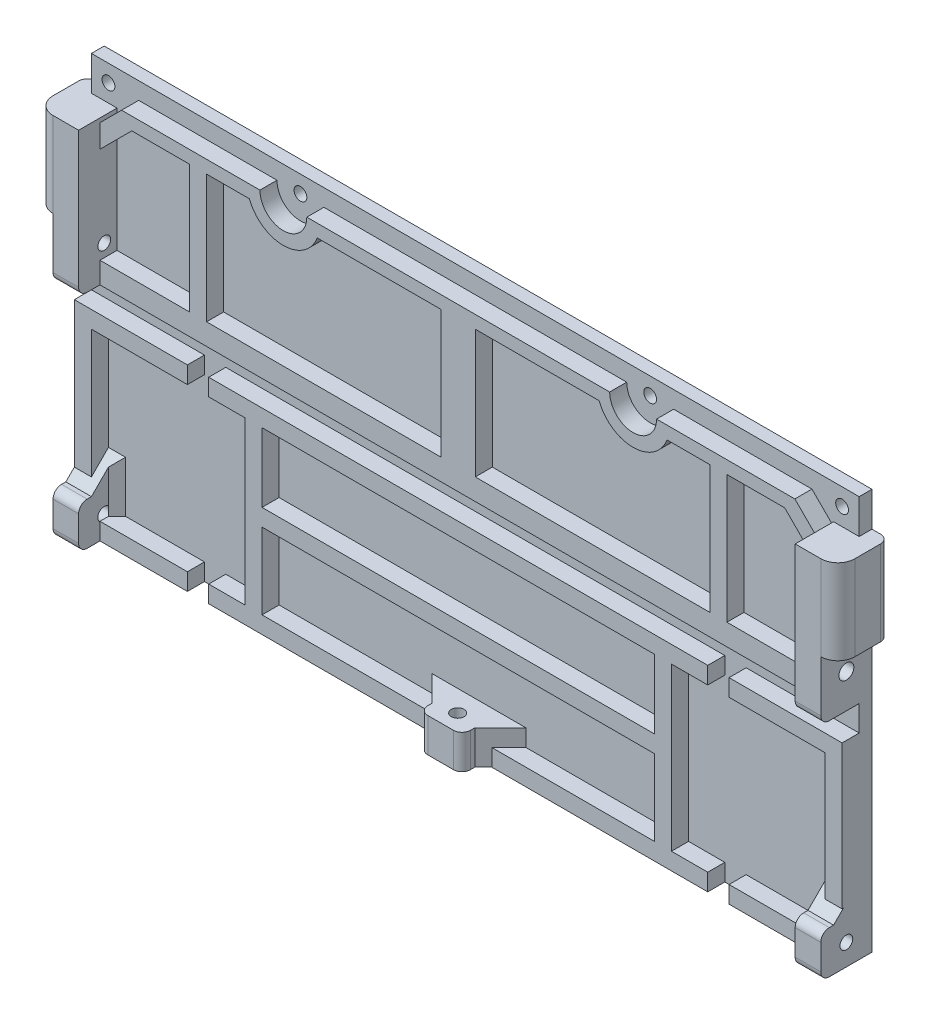
SolidWorks part; units mm, degrees
material "АБС-2020, черный"
ref_plane "Спереди" through (0, 0, 0) normal (0, 0, 1) x (1, 0, 0)
ref_plane "Сверху" through (0, 0, 0) normal (0, 1, 0) x (1, 0, 0)
ref_plane "Справа" through (0, 0, 0) normal (1, 0, 0) x (0, 0, -1)
other "Configuration Table"
sketch "Эскиз1" plane through (0, 0, 0) normal (0, 0, 1) x (1, 0, 0)
  line L1 (0, 0) -> (180, 0)
  line L2 (0, 0) -> (0, -94)
  line L3 (0, -94) -> (180, -94)
  line L4 (180, 0) -> (180, -94)
  dimension "D1" = 94
  dimension "D2" = 180
extrude "Бобышка-Вытянуть1" add sketch "Эскиз1" along normal blind 3
sketch "Эскиз2" plane through (0, 0, 3) normal (0, 0, 1) x (1, 0, 0)
  line L1 (0, -94) -> (6, -94)
  line L2 (0, -94) -> (0, -84)
  line L3 (0, -84) -> (6, -84)
  line L4 (6, -94) -> (6, -84)
  line L5 (180, -94) -> (174, -94)
  line L6 (180, -94) -> (180, -84)
  line L7 (180, -84) -> (174, -84)
  line L8 (174, -94) -> (174, -84)
  line L18 (0, -94) -> (180, -94) construction
  line L19 (180, 0) -> (0, 0) construction
  line L20 (180, -8.1) -> (174, -8.1)
  line L21 (180, -8.1) -> (180, -42)
  line L22 (180, -42) -> (174, -42)
  line L23 (174, -8.1) -> (174, -42)
  line L24 (0, -8.1) -> (6, -8.1)
  line L25 (0, -8.1) -> (0, -42)
  line L26 (0, -42) -> (6, -42)
  line L27 (6, -8.1) -> (6, -42)
  line L29 (85.876, -94) -> (95.876, -94)
  line L30 (85.876, -94) -> (85.876, -86)
  line L31 (85.876, -86) -> (95.876, -86)
  line L32 (95.876, -94) -> (95.876, -86)
  point P40 (90.876, -94)
  dimension "D1" = 10
  dimension "D2" = 6
  dimension "D3" = 10
  dimension "D4" = 6
  dimension "D12" = 8.1
  dimension "D13" = 8.1
  dimension "D15" = 10
  dimension "D16" = 5
  dimension "D17" = 8
extrude "Бобышка-Вытянуть2" add sketch "Эскиз2" along normal blind 9
chamfer "Фаска1" distance 6 angle 45 2 edges at (3, -84, 3) (177, -84, 3)
sketch "Эскиз3" plane through (180, 0, 0) normal (1, 0, 0) x (0, 0, -1)
  line L0 (0, -94) -> (0, 0) construction
  line L1 (-12, -94) -> (0, -94) construction
  line L2 (-3, 0) -> (0, 0) construction
  circle A0 centre (-6, -89) radius 1.5
  circle A2 centre (-6, -34) radius 1.75
  dimension "D1" = 3
  dimension "D7" = 3.5
  dimension "D2" = 6
  dimension "D3" = 5
  dimension "D6" = 34
extrude "Вырез-Вытянуть1" cut sketch "Эскиз3" against normal blind 8
sketch "Эскиз4" plane through (0, 0, 3) normal (0, 0, 1) x (1, 0, 0)
  line L0 (0, -84) -> (0, -94) construction
  line L1 (180, -94) -> (180, -84) construction
  line L2 (180, 0) -> (0, 0) construction
  circle A0 centre (4, -4) radius 1.5
  circle A1 centre (176, -4) radius 1.5
  circle A2 centre (49, -4) radius 1.5
  circle A3 centre (131, -4) radius 1.5
  dimension "D7" = 3
  dimension "D4" = 3
  dimension "D5" = 3
  dimension "D1" = 4
  dimension "D2" = 4
  dimension "D3" = 4
  dimension "D6" = 45
  dimension "D8" = 45
extrude "Вырез-Вытянуть2" cut sketch "Эскиз4" against normal through all
sketch "Эскиз5" plane through (0, 0, 3) normal (0, 0, 1) x (1, 0, 0)
  line L0 (44, -72.183) -> (44, -90)
  line L2 (40, -51.9927) -> (40, -90)
  line L4 (44, -51.9927) -> (44, -68.183)
  line L5 (180, -78) -> (180, -42) construction
  line L7 (136, -51.9927) -> (136, -68.183)
  line L9 (140, -51.9927) -> (140, -90)
  line L10 (0, -42) -> (0, -78) construction
  line L11 (180, 0) -> (0, 0) construction
  line L13 (27, -4.5) -> (27, -37)
  line L15 (31, -4.5) -> (31, -37)
  line L16 (44, -68.183) -> (136, -68.183)
  line L18 (149, -4.5) -> (149, -37)
  line L20 (153, -4.5) -> (153, -37)
  line L21 (27, -4.5) -> (31, -4.5)
  line L22 (149, -4.5) -> (153, -4.5)
  line L23 (0, 0) -> (0, -8.1) construction
  line L24 (180, -8.1) -> (180, 0) construction
  line L25 (174, -8.1) -> (174, -42) construction
  line L26 (86, -4.5) -> (94, -4.5)
  line L27 (86, -4.5) -> (86, -37)
  line L29 (94, -4.5) -> (94, -37)
  line L31 (6, -42) -> (6, -37)
  line L32 (6, -37) -> (27, -37)
  line L33 (174, -42) -> (174, -37)
  line L34 (31, -37) -> (86, -37)
  line L35 (94, -37) -> (149, -37)
  line L36 (153, -37) -> (174, -37)
  line L37 (6, -42) -> (174, -42)
  line L39 (0, -48) -> (0, -51.9927)
  line L40 (4, -51.9927) -> (40, -51.9927)
  line L41 (180, -48) -> (180, -51.9932)
  line L45 (44, -51.9927) -> (136, -51.9927)
  line L46 (140, -51.9927) -> (176, -51.9927)
  line L47 (0, -48) -> (180, -48)
  line L48 (6, -90) -> (40, -90)
  line L49 (6, -94) -> (6, -84) construction
  line L50 (174, -84) -> (174, -94) construction
  line L51 (6, -90) -> (6, -94)
  line L53 (44, -90) -> (136, -90)
  line L54 (140, -90) -> (174, -90)
  line L55 (6, -94) -> (174, -94)
  line L56 (174, -94) -> (180, -94) construction
  line L57 (174, -94) -> (174, -90)
  line L58 (44, -72.183) -> (136, -72.183)
  line L60 (136, -72.183) -> (136, -90)
  line L62 (180, -81.7054) -> (176, -81.7054)
  line L63 (180, -81.7054) -> (180, -51.9932)
  line L65 (176, -81.7054) -> (176, -51.9927)
  line L66 (0, -82.0861) -> (4, -82.0861)
  line L67 (0, -82.0861) -> (0, -51.9927)
  line L69 (4, -82.0861) -> (4, -51.9927)
  line L71 (0, -84) -> (0, -78) construction
  line L72 (180, -78) -> (180, -84) construction
  point P16 (-0.0298, -51.9978)
  point P21 (0, 0)
  point P65 (0, -82.0861)
  point P68 (0, 0)
  point P69 (180.0768, -52.0336)
  point P70 (180, -81.7054)
  dimension "D12" = 8
  dimension "D2" = 4
  dimension "D3" = 40
  dimension "D4" = 40
  dimension "D5" = 4
  dimension "D6" = 4
  dimension "D7" = 27
  dimension "D8" = 4
  dimension "D9" = 4.5
  dimension "D10" = 4
  dimension "D11" = 27
  dimension "D13" = 55
  dimension "D14" = 55
  dimension "D15" = 4
extrude "Бобышка-Вытянуть3" add sketch "Эскиз5" along normal blind 4
chamfer "Фаска3" distance 2 angle 45 2 edges at (174, -84, 3) (6, -84, 3)
sketch "Эскиз6" plane through (180, 0, 0) normal (1, 0, 0) x (0, 0, -1)
  line L0 (0, -94) -> (0, 0) construction
  line L1 (-12, -8.1) -> (0, -8.1)
  line L2 (-12, -8.1) -> (-12, -28)
  line L3 (-12, -28) -> (0, -28)
  line L4 (0, -8.1) -> (0, -28)
  line L5 (-3, 0) -> (0, 0) construction
  dimension "D1" = 28
  dimension "D2" = 8.1
extrude "Бобышка-Вытянуть4" add sketch "Эскиз6" along normal blind 4
fillet "Скругление1" radius 4 1 edges at (184, -18.05, 12)
sketch "Эскиз7" plane through (0, 0, 0) normal (-1, 0, 0) x (0, 0, 1)
  line L0 (12, -8.1) -> (12, -42) construction
  line L1 (0, -8.1) -> (12, -8.1)
  line L2 (0, -8.1) -> (0, -28)
  line L3 (0, -28) -> (12, -28)
  line L4 (12, -8.1) -> (12, -28)
  line L5 (3, 0) -> (0, 0) construction
  dimension "D1" = 28
extrude "Бобышка-Вытянуть5" add sketch "Эскиз7" along normal blind 4
fillet "Скругление2" radius 4 1 edges at (-4, -18.05, 12)
fillet "Скругление3" radius 2 2 edges at (184, -18.05, 0) (-4, -18.05, 0)
sketch "Эскиз8" plane through (0, -94, 0) normal (0, -1, 0) x (1, 0, 0)
  line L1 (85.876, 12) -> (85.876, 7) construction
  line L2 (0, 0) -> (180, 0) construction
  circle A0 centre (90.876, 8) radius 1.5
  dimension "D3" = 3
  dimension "D2" = 5
  dimension "D4" = 8
extrude "Вырез-Вытянуть3" cut sketch "Эскиз8" against normal blind 10
sketch "Эскиз9" plane through (0, 0, 0) normal (-1, 0, 0) x (0, 0, 1)
  line L0 (0, -28) -> (0, -94) construction
  line L1 (12, -94) -> (0, -94) construction
  line L2 (3, 0) -> (0, 0) construction
  circle A0 centre (6, -89) radius 1.5
  circle A1 centre (6, -34) radius 1.5
  point P8 (6, -35.4891)
  dimension "D1" = 3
  dimension "D2" = 3
  dimension "D3" = 34
  dimension "D4" = 6
  dimension "D5" = 5
extrude "Вырез-Вытянуть4" cut sketch "Эскиз9" against normal blind 6
chamfer "Фаска4" distance 6 angle 45 2 edges at (95.876, -88, 3) (85.876, -88, 3)
fillet "Скругление4" radius 2 8 edges at (177, -84, 12) (3, -84, 12) (3, -42, 12) (3, -94, 12) (177, -42, 12) (85.876, -90, 12) (95.876, -90, 12) (177, -94, 12)
sketch "Эскиз10" plane through (0, 0, 3) normal (0, 0, 1) x (1, 0, 0)
  line L0 (11.0731, -4) -> (43.5, -4)
  line L1 (6, -14.4642) -> (13.4642, -7)
  line L2 (6, -37) -> (6, -8.1) construction
  line L3 (13.4642, -7) -> (41.047, -7)
  line L4 (166.5358, -7) -> (174, -14.4642)
  line L5 (174, -8.1) -> (174, -40) construction
  line L6 (174, -14.4642) -> (174, -9.0731)
  line L7 (174, -8.1) -> (174, -37) construction
  line L9 (174, -9.0731) -> (168.9269, -4)
  line L10 (6, -9.0731) -> (11.0731, -4)
  line L11 (54.5, -4) -> (125.5, -4)
  line L12 (56.953, -7) -> (123.047, -7)
  line L13 (6, -40) -> (6, -8.1) construction
  line L14 (138.953, -7) -> (166.5358, -7)
  line L15 (136.5, -4) -> (168.9269, -4)
  line L16 (6, -9.0731) -> (6, -14.4642)
  arc A0 (125.5, -4) -> (136.5, -4) centre (131, -4) ccw
  arc A1 (43.5, -4) -> (54.5, -4) centre (49, -4) ccw
  arc A4 (41.047, -7) -> (56.953, -7) centre (49, -4) ccw
  arc A5 (123.047, -7) -> (138.953, -7) centre (131, -4) ccw
  point P1 (64, -4)
  point P8 (49, -4)
  line M8 (6, -8.1) -> (6, -37)
  line M10 (27, -37) -> (27, -4.5)
  line M11 (27, -4.5) -> (31, -4.5)
  line M12 (31, -4.5) -> (31, -37)
  line M14 (86, -37) -> (86, -4.5)
  line M15 (86, -4.5) -> (94, -4.5)
  line M16 (94, -4.5) -> (94, -37)
  line M18 (149, -37) -> (149, -4.5)
  line M19 (149, -4.5) -> (153, -4.5)
  line M20 (153, -4.5) -> (153, -37)
  line M22 (174, -37) -> (174, -8.1)
  dimension "D1" = 17
  dimension "D5" = 17
  dimension "D2" = 3
  dimension "D3" = 45
  dimension "D4" = 45
extrude "Бобышка-Вытянуть6" add sketch "Эскиз10" along normal blind 4 contours L12 A5 L15 A0 L11 A1 L0 L10 L1 L3 A4 M8 M10 M11 M12 M14 M15 M16 | A5 L14 L4 L9 L15 M18 M19 M20 M22 region at (27.2866, -4.1683, 3)
sketch "Эскиз11" plane through (0, 0, 7) normal (0, 0, 1) x (1, 0, 0)
  line L0 (180, -48) -> (0, -48) construction
  line L1 (148.5, -48) -> (153.5, -48)
  line L2 (148.5, -48) -> (148.5, -94)
  line L3 (148.5, -94) -> (153.5, -94)
  line L4 (153.5, -48) -> (153.5, -94)
  line L5 (97.876, -94) -> (174, -94) construction
  line L6 (6, -94) -> (83.876, -94) construction
  line L7 (26.5, -48) -> (31.5, -48)
  line L8 (26.5, -48) -> (26.5, -94)
  line L9 (26.5, -94) -> (31.5, -94)
  line L10 (31.5, -48) -> (31.5, -94)
  line L12 (0, -86) -> (0, -92) construction
  dimension "D1" = 5
  dimension "D2" = 5
  dimension "D4" = 26.5
extrude "Вырез-Вытянуть5" cut sketch "Эскиз11" against normal blind 4
